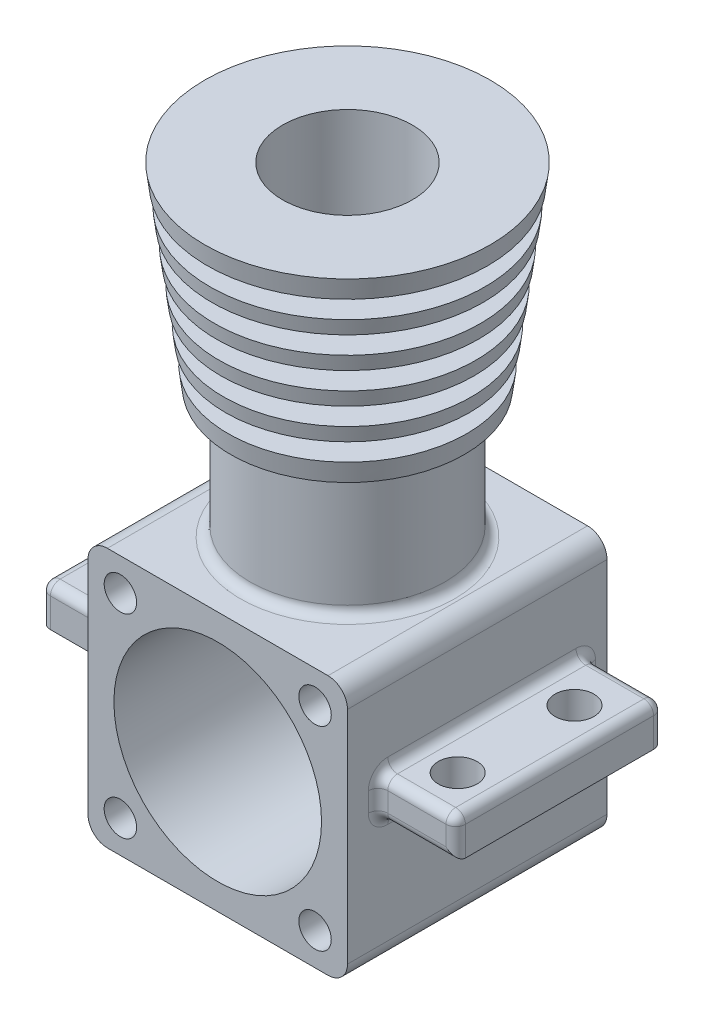
SolidWorks part; units mm, degrees
ref_plane "Front Plane" through (0, 0, 0) normal (0, 0, 1) x (1, 0, 0)
ref_plane "Top Plane" through (0, 0, 0) normal (0, 1, 0) x (1, 0, 0)
ref_plane "Right Plane" through (0, 0, 0) normal (1, 0, 0) x (0, 0, -1)
sketch "Sketch1" plane through (0, 0, 0) normal (0, 0, 1) x (1, 0, 0)
  line L1 (-19.9823, 19.9654) -> (20.0177, 19.9654)
  line L2 (-19.9823, 19.9654) -> (-19.9823, -20.0346)
  line L3 (-19.9823, -20.0346) -> (20.0177, -20.0346)
  line L4 (20.0177, 19.9654) -> (20.0177, -20.0346)
  line L5 (-19.9823, 19.9654) -> (20.0177, -20.0346) construction
  line L6 (-19.9823, -20.0346) -> (20.0177, 19.9654) construction
  line L7 (-14.9823, 14.9654) -> (15.0177, 14.9654) construction
  line L8 (-14.9823, 14.9654) -> (-14.9823, -15.0346) construction
  line L9 (-14.9823, -15.0346) -> (15.0177, -15.0346) construction
  line L10 (15.0177, 14.9654) -> (15.0177, -15.0346) construction
  line L11 (-14.9823, 14.9654) -> (15.0177, -15.0346) construction
  line L12 (-14.9823, -15.0346) -> (15.0177, 14.9654) construction
  circle A0 centre (-14.9823, 14.9654) radius 2.5
  circle A1 centre (15.0177, 14.9654) radius 2.5
  circle A2 centre (15.0177, -15.0346) radius 2.5
  circle A3 centre (-14.9823, -15.0346) radius 2.5
  circle A4 centre (0.0177, -0.0346) radius 16
  point P0 (0.0177, -0.0346)
  point P7 (0.0177, -0.0346)
  dimension "D4" = 5
  dimension "D5" = 32
  dimension "D1" = 40
  dimension "D2" = 40
  dimension "D3" = 5
extrude "Boss-Extrude1" add sketch "Sketch1" along normal mid plane 40
fillet "Fillet2" radius 3 4 edges at (20.0177, -20.0346, 0) (-19.9823, -20.0346, 0) (20.0177, 19.9654, 0) (-19.9823, 19.9654, 0)
sketch "Sketch2" plane through (0, 0, 0) normal (0, 0, 1) x (1, 0, 0)
  line L0 (0.0177, 19.9654) -> (0.0177, 69.9654)
  line L1 (17.0177, 19.9654) -> (-16.9823, 19.9654) construction
  line L2 (0.0177, 69.9654) -> (-21.9823, 69.9654)
  line L3 (-21.9823, 69.9654) -> (-17.9823, 39.9654)
  line L4 (-17.9823, 39.9654) -> (-14.9823, 39.9654)
  line L5 (-14.9823, 39.9654) -> (-14.9823, 19.9654)
  line L6 (-14.9823, 19.9654) -> (0.0177, 19.9654)
  point P4 (-14.9823, 29.9654)
  dimension "D1" = 22
  dimension "D2" = 50
  dimension "D3" = 15
  dimension "D4" = 20
  dimension "D5" = 18
revolve "Revolve2" add sketch "Sketch2" angle 360 about L0
sketch "Sketch7" plane through (0, 0, 0) normal (0, 0, 1) x (1, 0, 0)
  line L0 (-29.9823, 45.9654) -> (-11.9823, 45.9654)
  line L1 (-11.9823, 45.9654) -> (-11.9823, 42.9654)
  line L2 (-11.9823, 42.9654) -> (-29.9823, 42.9654)
  line L3 (-29.9823, 42.9654) -> (-29.9823, 45.9654)
  line L4 (-17.9823, 39.9654) -> (18.0177, 39.9654) construction
  line L5 (0.0177, -20.0346) -> (0.0177, 42.9654) construction
  line L6 (-16.9823, -20.0346) -> (17.0177, -20.0346) construction
  line L8 (0.0177, 42.9654) -> (0.0177, 69.9654) construction
  line L9 (22.0177, 69.9654) -> (-21.9823, 69.9654) construction
  dimension "D1" = 3
  dimension "D2" = 3
  dimension "D3" = 30
  dimension "D4" = 12
revolve "Cut-Revolve3" cut sketch "Sketch7" angle 360 about L8
pattern_linear "LPattern1" count 5 spacing 5.25 along (0, 1, 0) of "Cut-Revolve3"
sketch "Sketch8" plane through (0, 69.9654, 0) normal (0, 1, 0) x (1, 0, 0)
  circle A0 centre (0.0177, 0) radius 10
  dimension "D1" = 20
extrude "Cut-Extrude1" cut sketch "Sketch8" against normal blind 70 contours A0
sketch "Sketch10" plane through (0, 0, 0) normal (0, 1, 0) x (1, 0, 0)
  line L1 (-19.9823, -20) -> (-19.9823, 20) construction
  line L4 (-19.9823, -15.2872) -> (-19.9823, 16.7128)
  line L5 (0, 29.92) -> (0, -33.2651) construction
  line L7 (-19.9823, 16.7128) -> (-31.9823, 16.7128)
  line L8 (-31.9823, 16.7128) -> (-31.9823, -15.2872)
  line L9 (-31.9823, -15.2872) -> (-19.9823, -15.2872)
  line L10 (-19.9823, 16.7128) -> (-19.9823, -15.2872)
  circle A0 centre (-26, 9) radius 3
  circle A1 centre (-26, -9) radius 3
  dimension "D5" = 6
  dimension "D1" = 18
  dimension "D2" = 12
  dimension "D3" = 32
  dimension "D4" = 26
extrude "Boss-Extrude2" add sketch "Sketch10" along normal blind 6 contours L8 L9 L4 L7 A1 A0 region at (-25.9792, 0, -0.8359)
mirror "Mirror1" about plane through (0, 0, 0) normal (1, 0, 0) of "Boss-Extrude2"
fillet "Fillet4" radius 1.5 19 edges at (20.0177, 0, -0.7128) (20.0177, 6, -0.7128) (20.0177, 3, 15.2872) (26, 0, 15.2872) (20.0177, 3, -16.7128) (31.9823, 3, 15.2872) (31.9823, 3, -16.7128) (26, 6, -16.7128) (31.9823, 6, -0.7128) (26, 6, 15.2872) (15.0177, 19.9654, 0) (-19.9823, 6, -0.7128) (-19.9823, 3, -16.7128) (-31.9823, 3, -16.7128) (-19.9823, 3, 15.2872) (-31.9823, 3, 15.2872) (-25.9823, 6, -16.7128) (-25.9823, 6, 15.2872) (-31.9823, 6, -0.7128)
